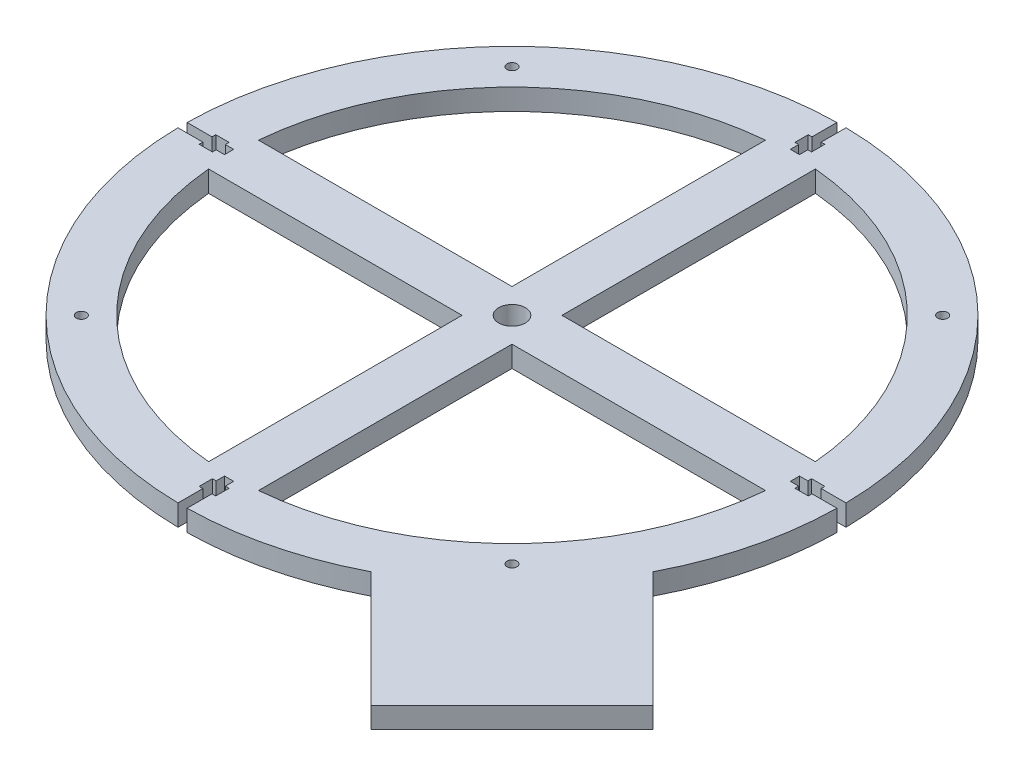
SolidWorks part; units mm, degrees
ref_plane "Front Plane" through (0, 0, 0) normal (0, 0, 1) x (1, 0, 0)
ref_plane "Top Plane" through (0, 0, 0) normal (0, 1, 0) x (1, 0, 0)
ref_plane "Right Plane" through (0, 0, 0) normal (1, 0, 0) x (0, 0, -1)
sketch "Sketch1" plane through (0, 0, 0) normal (0, 1, 0) x (1, 0, 0)
  line L0 (0, -99) -> (0, 99) construction
  line L1 (-99, 0) -> (99, 0) construction
  line L2 (-98.7155, -7.5) -> (98.7155, -7.5)
  line L3 (7.5, -98.7155) -> (7.5, 98.7155)
  line L4 (-98.7155, 7.5) -> (98.7155, 7.5)
  line L5 (-7.5, -98.7155) -> (-7.5, 98.7155)
  line L6 (-7.5, -99) -> (-7.5, 99) construction
  line L7 (7.5, -99) -> (7.5, 99) construction
  line L8 (-99, -7.5) -> (99, -7.5) construction
  line L9 (-99, 7.5) -> (99, 7.5) construction
  line L11 (80.2566, -122.683) -> (122.683, -80.2566)
  line L16 (101.4698, -101.4698) -> (70.0036, -70.0036) construction
  line L17 (122.683, -80.2566) -> (87.9253, -45.4989)
  line L23 (80.2566, -122.683) -> (45.4989, -87.9253)
  line L33 (122.683, -80.2566) -> (91.2168, -48.7904) construction
  line L34 (80.2566, -122.683) -> (48.7904, -91.2168) construction
  circle A0 centre (0, 0) radius 100 construction
  circle A1 centre (0, 0) radius 99
  circle A2 centre (0, 0) radius 84
  point P7 (0, 0)
  point P11 (0, 0)
  dimension "D1" = 200
  dimension "D2" = 1
  dimension "D3" = 15
  dimension "D6" = 45
  dimension "D8" = 43.5
  dimension "D4" = 7.5
  dimension "D5" = 7.5
  dimension "D11" = 30
  dimension "D12" = 30
extrude "Boss-Extrude1" add sketch "Sketch1" along normal mid plane 6.35 contours A2 L2 A1 L5 | A2 L4 A1 L2 | A2 L5 A1 L4 | A2 L3 A1 L5 | A2 L4 A1 L3 | A2 L2 A1 L4 | A2 L3 A1 L2 | A2 L5 A1 L3 | L5 A2 L3 L2 | L4 A2 L2 L5 | L3 A2 L5 L4 | L2 A2 L4 L3 | L5 L2 L3 L4 | A1 | A1 L23 L17 region at (-91.3966, 0, 0) region at (-59.642, 0, 59.642) region at (-45.6942, 0, 0) region at (-59.642, 0, -59.642) region at (0, 0, 91.3966) region at (0, 0, 0) region at (0, 0, 45.6942) region at (0, 0, -91.3966) region at (59.642, 0, 59.642) region at (45.6942, 0, 0) region at (0, 0, -45.6942) region at (59.642, 0, -59.642) region at (85.1787, 0, 85.1787) region at (91.3966, 0, 0)
sketch "Sketch2" plane through (0, 0, 0) normal (0, 1, 0) x (1, 0, 0)
  line L0 (-1.375, 85) -> (-1.375, 99)
  line L1 (-1.375, 85) -> (1.375, 85)
  line L2 (-1.375, 99) -> (1.375, 99)
  line L3 (1.375, 85) -> (1.375, 99)
  line L4 (-1.375, 85) -> (1.375, 99) construction
  line L5 (-1.375, 99) -> (1.375, 85) construction
  line L6 (-2.5, 87.5) -> (-2.5, 91.5)
  line L7 (-2.5, 87.5) -> (2.5, 87.5)
  line L8 (-2.5, 91.5) -> (2.5, 91.5)
  line L9 (2.5, 87.5) -> (2.5, 91.5)
  line L10 (-2.5, 87.5) -> (2.5, 91.5) construction
  line L11 (-2.5, 91.5) -> (2.5, 87.5) construction
  line L12 (0, -1000) -> (0, 49000) construction
  line L13 (-1000, 0) -> (49000, 0) construction
  circle A0 centre (0, 0) radius 99 construction
  point P1 (0, 92)
  point P2 (0, 89.5)
  dimension "D1" = 2.75
  dimension "D2" = 14
  dimension "D3" = 4
  dimension "D4" = 5
  dimension "D5" = 2.5
extrude "Cut-Extrude1" cut sketch "Sketch2" against normal through all both and the other way through all contours L7 L0 L1 L3 | L8 L0 L7 L3 | L7 L9 L8 L3 | L0 L8 L3 L2 | L8 L6 L7 L0 region at (0, 0, -86.25) region at (-1.9375, 0, -89.5) region at (0, 0, -89.5) region at (0, 0, -95.25) region at (1.9375, 0, -89.5)
pattern_circular "CirPattern1" count 4 over 360 about axis through (0, 3.175, 0) along (0, 1, 0) of "Cut-Extrude1"
hole_wizard "Ø3.0 (3) Diameter Hole1" positions "Sketch3" profile "Sketch4" hole size "Ø3.0" standard "ANSI Metric" end condition up to next
sketch "Sketch3" plane through (0, 3.175, 0) normal (0, 1, 0) x (1, 0, 0)
  line L0 (-70.0036, -70.0036) -> (70.0036, 70.0036) construction
  line L2 (-70.0036, 70.0036) -> (70.0036, -70.0036) construction
  line L4 (70.0036, 70.0036) -> (59.397, 59.397)
  line L6 (70.0036, -70.0036) -> (59.397, -59.397)
  line L8 (-70.0036, -70.0036) -> (-59.397, -59.397)
  line L10 (-70.0036, 70.0036) -> (-59.397, 59.397)
  arc A2 (83.6645, 7.5) -> (7.5, 83.6645) centre (0, 0) ccw construction
  arc A3 (7.5, -83.6645) -> (83.6645, -7.5) centre (0, 0) ccw construction
  arc A4 (-83.6645, -7.5) -> (-7.5, -83.6645) centre (0, 0) ccw construction
  arc A5 (-7.5, 83.6645) -> (-83.6645, 7.5) centre (0, 0) ccw construction
  circle A6 centre (0, 0) radius 99
  arc A7 (-1.375, 98.9905) -> (-98.9905, 1.375) centre (0, 0) ccw construction
  point P107 (0, 0)
  point P324 (0, 0)
  point P360 (-64.7003, 64.7003)
  point P362 (64.7003, 64.7003)
  point P364 (64.7003, -64.7003)
  point P366 (-64.7003, -64.7003)
sketch "Sketch4" plane through (-64.7003, 3.175, 64.7003) normal (1, 0, 0) x (0, 0, 1)
  line L0 (0, 0) -> (0, 6.35)
  line L1 (0, 6.35) -> (1.5, 6.35)
  line L2 (1.5, 6.35) -> (1.5, 0)
  line L5 (1.5, 0) -> (0, 0)
  line L11 (0, -6.35) -> (0, 107.95) construction
  dimension "Thru Hole Dia." = 3
  dimension "Thru Hole Depth" = 6.35
hole_wizard "Ø8.0 (8) Diameter Hole1" positions "Sketch5" profile "Sketch6" hole size "Ø8.0" standard "ANSI Metric" end condition up to next
sketch "Sketch5" plane through (0, 3.175, 0) normal (0, 1, 0) x (1, 0, 0)
  point P0 (0, 0)
sketch "Sketch6" plane through (0, 3.175, 0) normal (1, 0, 0) x (0, 0, 1)
  line L0 (0, 0) -> (0, 6.35)
  line L1 (0, 6.35) -> (4, 6.35)
  line L2 (4, 6.35) -> (4, 0)
  line L5 (4, 0) -> (0, 0)
  line L11 (0, -6.35) -> (0, 107.95) construction
  dimension "Thru Hole Dia." = 8
  dimension "Thru Hole Depth" = 6.35
